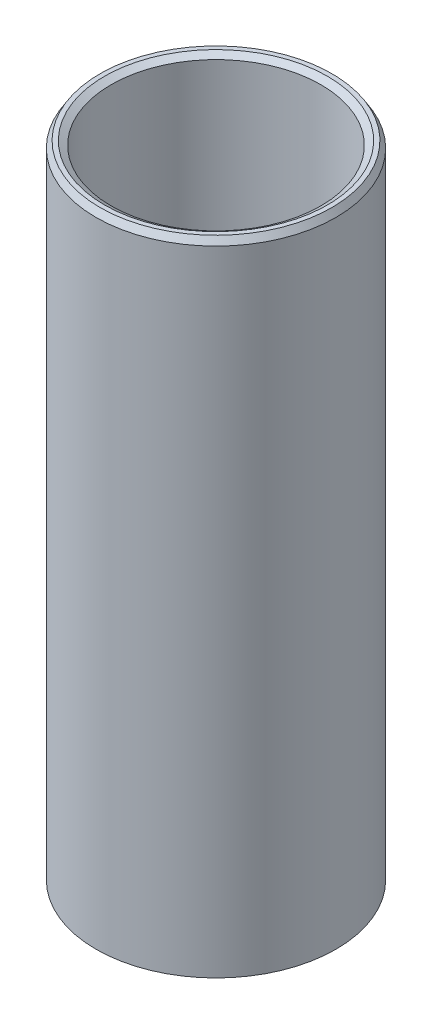
SolidWorks part; units mm, degrees
ref_plane "Front Plane" through (0, 0, 0) normal (0, 0, 1) x (1, 0, 0)
ref_plane "Top Plane" through (0, 0, 0) normal (0, 1, 0) x (1, 0, 0)
ref_plane "Right Plane" through (0, 0, 0) normal (1, 0, 0) x (0, 0, -1)
sketch "Sketch1" plane through (0, 0, 0) normal (0, 1, 0) x (1, 0, 0)
  circle A0 centre (0, 0) radius 40
  dimension "SLEEVE_OD" = 80
extrude "Boss-Extrude1" add sketch "Sketch1" along normal blind 214.8233
sketch "Sketch2" plane through (0, 0, 0) normal (0, 1, 0) x (1, 0, 0)
  circle A0 centre (0, 0) radius 34.9882
  dimension "BORE_D" = 69.9764
extrude "Cut-Extrude1" cut sketch "Sketch2" along normal through all
chamfer "Chamfer1" distance 2.1834 angle 31.657 4 edges at (0, 214.8233, 34.9882) (0, 0, 34.9882) (0, 0, 40) (0, 214.8233, 40) first distance on face at (0, 214.8233, 34.9882) first distance on face at (0, 0, 34.9882) first distance on face at (0, 214.8233, 40)
